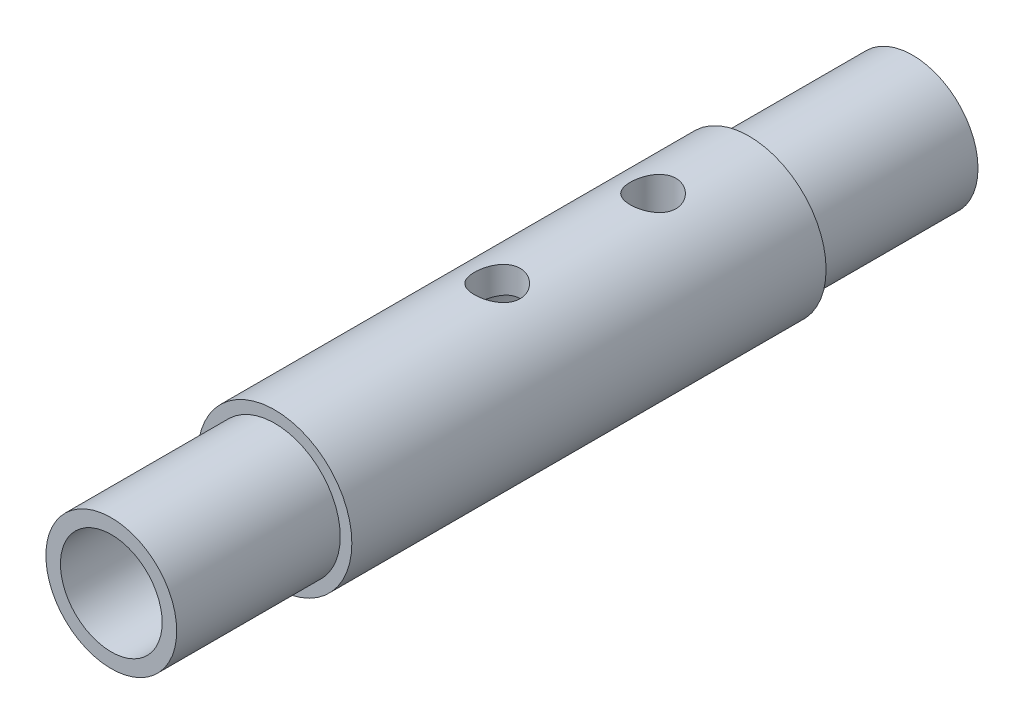
SolidWorks part; units mm, degrees
ref_plane "Front" through (0, 0, 0) normal (0, 0, 1) x (1, 0, 0)
ref_plane "Top" through (0, 0, 0) normal (0, 1, 0) x (1, 0, 0)
ref_plane "Right" through (0, 0, 0) normal (1, 0, 0) x (0, 0, -1)
sketch "Sketch1" plane through (0, 0, 0) normal (0, 0, 1) x (1, 0, 0)
  circle A0 centre (0, 0) radius 4
extrude "Extrude1" add sketch "Sketch1" along normal blind 10
sketch "Sketch2" plane through (0, 0, 0) normal (0, 0, -1) x (-1, 0, 0)
  circle A0 centre (0, 0) radius 2.5
sketch "Sketch4" plane through (0, 0, 10) normal (0, 0, 1) x (1, 0, 0)
  circle A0 centre (0, 0) radius 4.71
extrude "Extrude2" add sketch "Sketch4" along normal blind 29
extrude "Cut-Extrude1" cut sketch "Sketch2" against normal blind 20
sketch "Sketch5" plane through (0, 0, 39) normal (0, 0, 1) x (1, 0, 0)
  circle A0 centre (0, 0) radius 4
extrude "Extrude3" add sketch "Sketch5" along normal blind 10
sketch "Sketch6" plane through (0, 0, 49) normal (0, 0, 1) x (1, 0, 0)
  circle A0 centre (0, 0) radius 3.11
extrude "Cut-Extrude2" cut sketch "Sketch6" against normal blind 29
sketch "Sketch7" plane through (0, 0, 0) normal (0, 1, 0) x (1, 0, 0)
  line L0 (0, -10) -> (0, 0) construction
  circle A0 centre (0, -15.87) radius 1.4
  circle A1 centre (0, -25.4) radius 1.4
extrude "Cut-Extrude3" cut sketch "Sketch7" against normal through all and the other way through all
